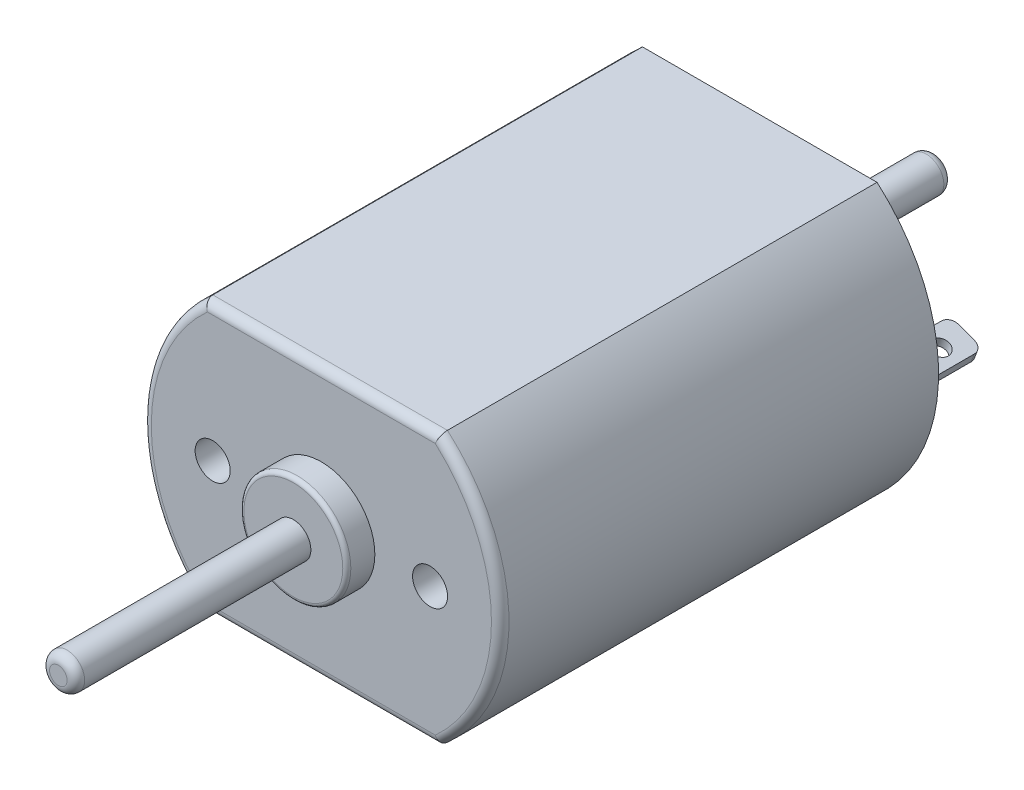
SolidWorks part; units mm, degrees
ref_plane "Front Plane" through (0, 0, 0) normal (0, 0, 1) x (1, 0, 0)
ref_plane "Top Plane" through (0, 0, 0) normal (0, 1, 0) x (1, 0, 0)
ref_plane "Right Plane" through (0, 0, 0) normal (1, 0, 0) x (0, 0, -1)
sketch "Sketch1" plane through (0, 0, 0) normal (0, 0, 1) x (1, 0, 0)
  line L1 (-18.4525, -7.7) -> (18.4525, -7.7)
  line L2 (-18.4525, -7.7) -> (-18.4525, 7.7)
  line L3 (-18.4525, 7.7) -> (18.4525, 7.7)
  line L4 (18.4525, -7.7) -> (18.4525, 7.7)
  line L5 (-18.4525, -7.7) -> (18.4525, 7.7) construction
  line L6 (-18.4525, 7.7) -> (18.4525, -7.7) construction
  circle A0 centre (0, 0) radius 10.2
  dimension "D1" = 20.4
  dimension "D2" = 15.4
extrude "Boss-Extrude1" add sketch "Sketch1" along normal blind 25 contours L3 A0 L1 region at (0, 0, 0)
fillet "Fillet1" radius 0.5 4 edges at (-10.2, 0, 25) (0, -7.7, 25) (10.2, 0, 25) (0, 7.7, 25)
sketch "Sketch2" plane through (0, 0, 25) normal (0, 0, 1) x (1, 0, 0)
  circle A0 centre (0, 0) radius 3.05
  dimension "D1" = 6.1
extrude "Boss-Extrude2" add sketch "Sketch2" along normal blind 1.6
sketch "Sketch3" plane through (0, 0, 26.6) normal (0, 0, 1) x (1, 0, 0)
  circle A0 centre (0, 0) radius 1
  dimension "D1" = 2
extrude "Boss-Extrude3" add sketch "Sketch3" along normal offset from surface (13.4 mm away) 15 up to face at (3.05, 0, 25) offset beyond the face yes
sketch "Sketch4" plane through (0, 0, 0) normal (0, 0, -1) x (-1, 0, 0)
  circle A0 centre (0, 0) radius 3.075
  dimension "D1" = 6.15
extrude "Boss-Extrude4" add sketch "Sketch4" along normal blind 2
fillet "Fillet2" radius 0.23 2 edges at (3.05, 0, 26.6) (-3.075, 0, -2)
sketch "Sketch5" plane through (0, 0, -2) normal (0, 0, -1) x (-1, 0, 0)
  circle A0 centre (0, 0) radius 1
  dimension "D1" = 2
extrude "Boss-Extrude6" add sketch "Sketch5" along normal offset from surface (8 mm away) 10 up to face at (-3.075, 0, 0) offset beyond the face yes
fillet "Fillet3" radius 0.5 2 edges at (1, 0, 40) (1, 0, -10)
sketch "Sketch6" plane through (0, 0, 0) normal (0, 0, -1) x (-1, 0, 0)
  line L0 (0, 0) -> (13.2626, 0) construction
  line L1 (7.0021, 1.7) -> (13.5461, 1.7) construction
  line L2 (7.4166, -1.7) -> (13.0226, -1.7) construction
  line L3 (7.4074, 1.7) -> (13.7175, 4.0384) construction
  line L4 (-7.4074, -1.7) -> (-12.4105, -3.554) construction
  line L6 (-8.2582, -2.2819) -> (-6.3829, -1.5869)
  line L7 (-8.2582, -2.2819) -> (-8.432, -1.8131)
  line L8 (-8.432, -1.8131) -> (-6.5566, -1.1181)
  line L9 (-6.3829, -1.5869) -> (-6.5566, -1.1181)
  line L10 (-8.2582, -2.2819) -> (-6.5566, -1.1181) construction
  line L11 (-8.432, -1.8131) -> (-6.3829, -1.5869) construction
  line L12 (8.432, 1.8131) -> (6.5566, 1.1181)
  line L13 (8.432, 1.8131) -> (8.2582, 2.2819)
  line L14 (8.2582, 2.2819) -> (6.3829, 1.5869)
  line L15 (6.5566, 1.1181) -> (6.3829, 1.5869)
  line L16 (8.432, 1.8131) -> (6.3829, 1.5869) construction
  line L17 (8.2582, 2.2819) -> (6.5566, 1.1181) construction
  circle A0 centre (0, 0) radius 7.6 construction
  circle A1 centre (7.4074, 1.7) radius 1.2
  circle A2 centre (-7.4074, -1.7) radius 1.2
  point P22 (-5.5624, -2.0505)
  point P23 (-5.1916, -1.2216)
  point P24 (9.6633, 2.1813)
  dimension "D4" = 15.2
  dimension "D6" = 2.4
  dimension "D1" = 1.7
  dimension "D2" = 1.7
  dimension "D3" = 3.4
  dimension "D5" = 20.333
  dimension "D7" = 2
  dimension "D8" = 0.5
extrude "Boss-Extrude7" add sketch "Sketch6" along normal blind 4.3 contours L6 L9 L8 L7 | L15 L12 L13 L14 region at (7.4074, -1.7, 0) region at (-7.4074, 1.7, 0)
extrude "Boss-Extrude8" add sketch "Sketch6<3>" along normal blind 0.3 contours A2 L9 L6 L7 L8 | A1 L12 L15 L14 L13 region at (-6.2414, 1.7, 0) region at (8.5735, -1.7, 0)
sketch "Sketch6<3>" plane through (0, 0, 0) normal (0, 0, -1) x (-1, 0, 0) same geometry as "Sketch6"
fillet "Fillet4" radius 0.5 4 edges at (-8.3451, 2.0475, -4.3) (-6.4697, 1.3525, -4.3) (6.4697, -1.3525, -4.3) (8.3451, -2.0475, -4.3)
sketch "Sketch7" plane through (0.2536, 0.6844, 0) normal (-0.3475, -0.9377, 0) x (0.9377, -0.3475, 0)
  line L0 (7.5366, -4.3) -> (7.5366, 1.7024) construction
  line L1 (8.0366, -4.3) -> (7.0366, -4.3) construction
  line L2 (-7.5366, -4.3) -> (-7.5366, 1.4762) construction
  line L3 (-8.0366, -4.3) -> (-7.0366, -4.3) construction
  line L4 (-7.5366, -2.8) -> (7.5366, -2.8) construction
  circle A0 centre (-7.5366, -2.8) radius 0.5
  circle A1 centre (7.5366, -2.8) radius 0.5
  dimension "D1" = 1
  dimension "D2" = 1.5
extrude "Cut-Extrude1" cut sketch "Sketch7" against normal through all and the other way through all
sketch "Sketch8" plane through (0, 0, 25) normal (0, 0, 1) x (1, 0, 0)
  line L0 (-6.2, 0) -> (6.2, 0) construction
  circle A0 centre (0, 0) radius 6.2 construction
  dimension "D1" = 12.4
hole_wizard "Ø2.0 (2) Diameter Hole1" positions "Sketch9" profile "Sketch10" hole size "Ø2.0" standard "ANSI Metric"
sketch "Sketch9" plane through (0, 0, 25) normal (0, 0, 1) x (1, 0, 0)
  point P0 (-6.2, 0)
  point P3 (6.2, 0)
sketch "Sketch10" plane through (-6.2, 0, 25) normal (1, 0, 0) x (0, -1, 0)
  line L0 (0, 0) -> (0, 2.6009)
  line L1 (0, 2.6009) -> (1, 2)
  line L2 (1, 2) -> (1, 0)
  line L5 (1, 0) -> (0, 0)
  line L10 (0, 2.6009) -> (-1, 2) construction
  line L11 (0, -6.35) -> (0, 107.95) construction
  dimension "Hole Dia." = 2
  dimension "Hole Depth" = 2
  dimension "Drill Angle" = 118
